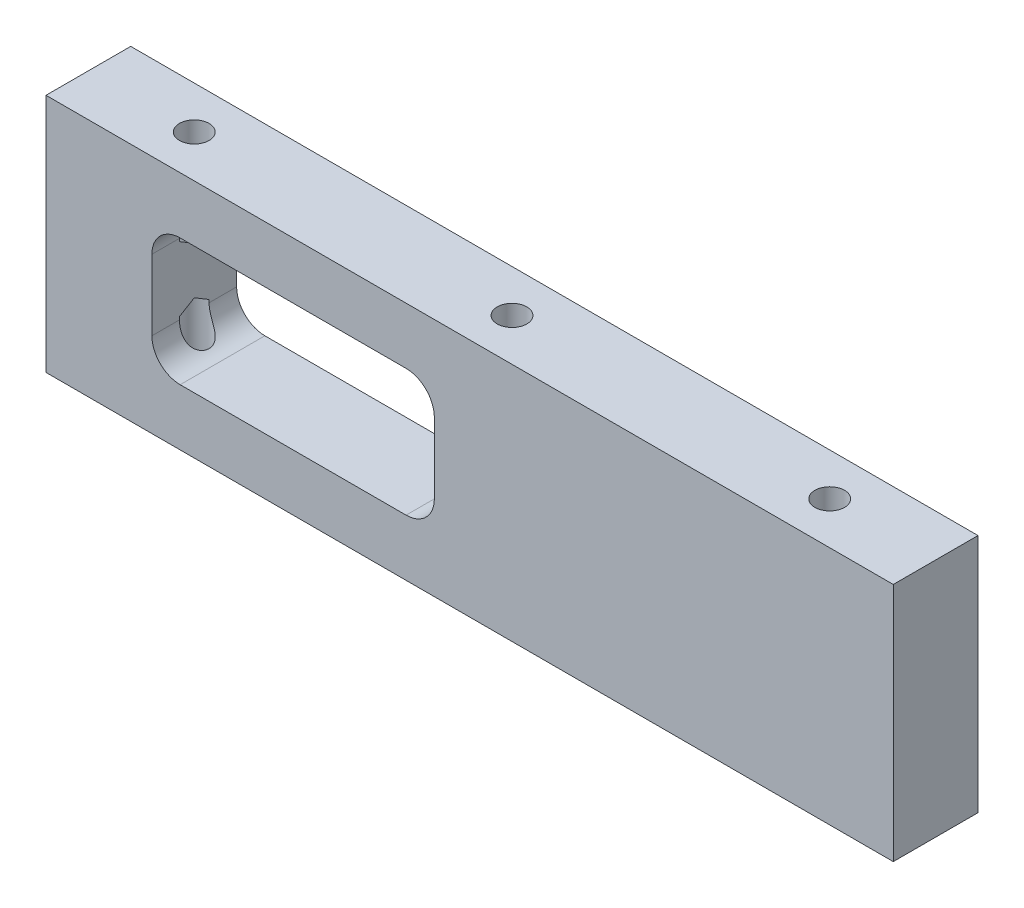
SolidWorks part; units mm, degrees
material "SKD11淬火HRC56-60"
ref_plane "前基準面" through (0, 0, 0) normal (0, 0, 1) x (1, 0, 0)
ref_plane "上基準面" through (0, 0, 0) normal (0, 1, 0) x (1, 0, 0)
ref_plane "右基準面" through (0, 0, 0) normal (1, 0, 0) x (0, 0, -1)
sketch "草图1" plane through (0, 0, 0) normal (0, 0, 1) x (1, 0, 0)
  line L1 (0, 0) -> (120, 0)
  line L2 (0, 0) -> (0, 34)
  line L3 (0, 34) -> (120, 34)
  line L4 (120, 0) -> (120, 34)
  dimension "D1" = 120
  dimension "D2" = 34
extrude "凸台-拉伸1" add sketch "草图1" along normal blind 12
sketch "草图2" plane through (0, 0, 12) normal (0, 0, 1) x (1, 0, 0)
  line L0 (0, 17) -> (120, 17) construction
  line L1 (55, 26) -> (15, 26)
  line L2 (55, 26) -> (55, 8)
  line L3 (55, 8) -> (15, 8)
  line L4 (15, 26) -> (15, 8)
  line L5 (0, 34) -> (0, 0) construction
  line L6 (120, 0) -> (120, 34) construction
  dimension "D1" = 18
  dimension "D2" = 15
  dimension "D3" = 40
extrude "切除-拉伸1" cut sketch "草图2" against normal through all
fillet "圆角1" radius 4 4 edges at (55, 26, 6) (55, 8, 6) (15, 8, 6) (15, 26, 6)
hole_wizard "M5 螺纹孔1" positions "草图4" profile "草图3" tap size "M5" standard "ISO"
sketch "草图4" plane through (0, 34, 0) normal (0, 1, 0) x (-1, 0, 0)
  line L0 (-120, 6) -> (0, 6) construction
  line L1 (-120, 12) -> (-120, 0) construction
  line L2 (0, 12) -> (0, 0) construction
  line L3 (-60, 0) -> (-60, 12) construction
  line L4 (-120, 0) -> (0, 0) construction
  line L5 (-120, 12) -> (0, 12) construction
  point P0 (-15, 6)
  point P1 (-60, 6)
  point P3 (-105, 6)
  dimension "D1" = 90
sketch "草图3" plane through (15, 34, 6) normal (1, 0, 0) x (0, 0, 1)
  line L0 (0, 0) -> (0, 13.6618)
  line L1 (0, 13.6618) -> (2.1, 12.4)
  line L2 (2.1, 12.4) -> (2.1, 0)
  line L5 (2.1, 0) -> (0, 0)
  line L10 (0, 13.6618) -> (-2.1, 12.4) construction
  line L11 (0, -6.35) -> (0, 107.95) construction
  dimension "螺纹孔钻头直径" = 4.2
  dimension "螺纹孔钻头深度" = 12.4
  dimension "导头角度" = 118
cosmetic thread "孔螺蚊线1" parameters "D1"=10, "D2"=5
cosmetic thread "孔螺蚊线2" parameters "D1"=10, "D2"=5
cosmetic thread "孔螺蚊线3" parameters "D1"=10, "D2"=5
hole_wizard "M5 螺纹孔2" positions "草图6" profile "草图5" tap size "M5" standard "ISO"
sketch "草图6" plane through (0, 0, 0) normal (0, -1, 0) x (1, 0, 0)
  line L0 (120, 6) -> (0, 6) construction
  line L1 (120, 12) -> (120, 0) construction
  line L2 (0, 12) -> (0, 0) construction
  line L3 (60, 0) -> (60, 12) construction
  line L4 (0, 0) -> (120, 0) construction
  line L5 (0, 12) -> (120, 12) construction
  point P0 (105, 6)
  point P1 (60, 6)
  point P3 (15, 6)
  dimension "D1" = 90
sketch "草图5" plane through (105, 0, 6) normal (1, 0, 0) x (0, 0, -1)
  line L0 (0, 0) -> (0, 13.6618)
  line L1 (0, 13.6618) -> (2.1, 12.4)
  line L2 (2.1, 12.4) -> (2.1, 0)
  line L5 (2.1, 0) -> (0, 0)
  line L10 (0, 13.6618) -> (-2.1, 12.4) construction
  line L11 (0, -6.35) -> (0, 107.95) construction
  dimension "螺纹孔钻头直径" = 4.2
  dimension "螺纹孔钻头深度" = 12.4
  dimension "导头角度" = 118
cosmetic thread "孔螺蚊线4" parameters "D1"=10, "D2"=5
cosmetic thread "孔螺蚊线5" parameters "D1"=10, "D2"=5
cosmetic thread "孔螺蚊线6" parameters "D1"=10, "D2"=5
